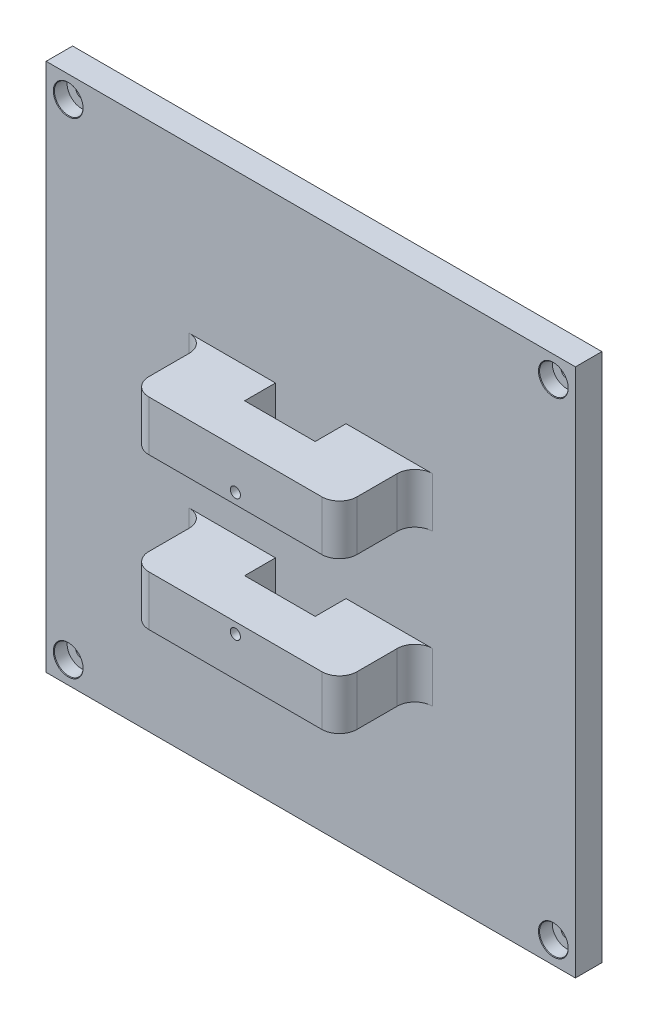
SolidWorks part; units mm, degrees
ref_plane "Front Plane" through (0, 0, 0) normal (1, 0, 0) x (0, 1, 0)
ref_plane "Top Plane" through (0, 0, 0) normal (0, 0, 1) x (0, 1, 0)
ref_plane "Right Plane" through (0, 0, 0) normal (0, 1, 0) x (-1, 0, 0)
sketch "Sketch1" plane through (0, 0, 0) normal (0, 0, 1) x (0, 1, 0)
  line L1 (-60, -60) -> (60, -60)
  line L2 (-60, -60) -> (-60, 60)
  line L3 (-60, 60) -> (60, 60)
  line L4 (60, -60) -> (60, 60)
  line L5 (-60, -60) -> (60, 60) construction
  line L6 (-60, 60) -> (60, -60) construction
  point P0 (0, 0)
  dimension "D1" = 120
  dimension "D2" = 120
extrude "Boss-Extrude1" add sketch "Sketch1" along normal blind 6
sketch "Sketch2" plane through (0, 0, 6) normal (0, 0, 1) x (1, 0, 0)
  line L0 (-60, 60) -> (-50, 60)
  line L1 (-60, 60) -> (-60, 50)
  line L2 (-60, 50) -> (-50, 50)
  line L3 (-50, 60) -> (-50, 50)
  line L4 (45, 60) -> (45, 45)
  line L5 (60, 45) -> (45, 45)
  line L6 (60, 60) -> (60, 45)
  line L7 (60, 60) -> (45, 60)
  line L8 (60, -60) -> (45, -60)
  line L9 (60, -60) -> (60, -45)
  line L10 (60, -45) -> (45, -45)
  line L11 (45, -60) -> (45, -45)
  line L12 (-45, -60) -> (-45, -45)
  line L13 (-60, -45) -> (-45, -45)
  line L14 (-60, -60) -> (-60, -45)
  line L15 (-60, -60) -> (-45, -60)
  circle A0 centre (-55, 55) radius 1.25
  point P28 (-55, 55)
  dimension "D2" = 2.5
  dimension "D4" = 5
  dimension "D1" = 10
  dimension "D3" = 10
  dimension "D5" = 5
hole_wizard "CBORE for M3 SBHCS1" positions "Sketch2" profile "Sketch7" counterbore size "M3" standard "ANSI Metric" end condition through all
sketch "Sketch7" plane through (-55, 55, 6) normal (1, 0, 0) x (0, -1, 0)
  line L0 (0, 0) -> (0, 6)
  line L1 (0, 6) -> (1.25, 6)
  line L3 (1.25, 6) -> (1.25, 3)
  line L4 (3.25, 3) -> (1.25, 3)
  line L5 (3.25, 3) -> (3.25, 0.125)
  line L6 (3.25, 0.125) -> (3.375, 0)
  line L7 (3.375, 0) -> (0, 0)
  line L8 (-3.25, 0.125) -> (-3.375, 0) construction
  line L11 (0, -6.35) -> (0, 107.95) construction
  dimension "Thru Hole Dia." = 2.5
  dimension "Thru Hole Depth" = 6
  dimension "C'Bore Dia." = 6.5
  dimension "C'Bore Depth" = 3
  dimension "Near C'Sink Dia." = 6.75
  dimension "Near C'Sink Angle" = 90
mirror "Mirror2" about plane through (0, 0, 0) normal (1, 0, 0) of "CBORE for M3 SBHCS1" second plane through (0, 0, 0) second plane normal (0, 1, 0)
sketch "Sketch3" plane through (0, 0, 6) normal (0, 0, 1) x (1, 0, 0)
  line L0 (3.3, 0) -> (-3.3, 0) construction
  line L1 (23.598, -22.8365) -> (-23.598, -22.8365)
  line L2 (23.598, -22.8365) -> (23.598, -11.5)
  line L3 (23.598, -11.5) -> (-23.598, -11.5)
  line L4 (-23.598, -22.8365) -> (-23.598, -11.5)
  line L5 (23.598, -22.8365) -> (-23.598, -11.5) construction
  line L6 (23.598, -11.5) -> (-23.598, -22.8365) construction
  line L7 (-23.598, 22.8365) -> (-23.598, 11.5)
  line L8 (23.598, 11.5) -> (-23.598, 11.5)
  line L9 (23.598, 22.8365) -> (23.598, 11.5)
  line L10 (23.598, 22.8365) -> (-23.598, 22.8365)
  point P0 (0, -17.1682)
  dimension "D1" = 11.5
extrude "Boss-Extrude2" add sketch "Sketch3" along normal blind 17.1
sketch "Sketch4" plane through (0, -22.8365, 0) normal (0, -1, 0) x (1, 0, 0)
  line L0 (-8, 6) -> (-8, 13)
  line L1 (-8, 6) -> (8, 6)
  line L2 (-8, 13) -> (8, 13)
  line L3 (8, 6) -> (8, 13)
  line L4 (-60, 6) -> (60, 6) construction
  line L5 (0, -3.3) -> (0, 3.3) construction
  dimension "D1" = 8
  dimension "D2" = 8
  dimension "D3" = 7
extrude "Cut-Extrude3" cut sketch "Sketch4" against normal through all
sketch "Sketch6" plane through (0, 0, 23.1) normal (0, 0, 1) x (1, 0, 0)
  line L0 (0, -12.705) -> (0, 12.705) construction
  line L1 (-23.598, 11.5) -> (23.598, 11.5) construction
  line L2 (12.705, 0) -> (-12.705, 0) construction
  circle A0 centre (0, 13.9) radius 1.15
  circle A1 centre (0, -13.9) radius 1.15
  dimension "D1" = 2.3
  dimension "D2" = 2.4
extrude "Cut-Extrude4" cut sketch "Sketch6" against normal blind 8
fillet "Fillet1" radius 4 8 edges at (-23.598, -17.1682, 6) (-23.598, 17.1682, 6) (23.598, 17.1682, 6) (23.598, -17.1682, 6) (-23.598, 17.1682, 23.1) (23.598, 17.1682, 23.1) (-23.598, -17.1682, 23.1) (23.598, -17.1682, 23.1)
